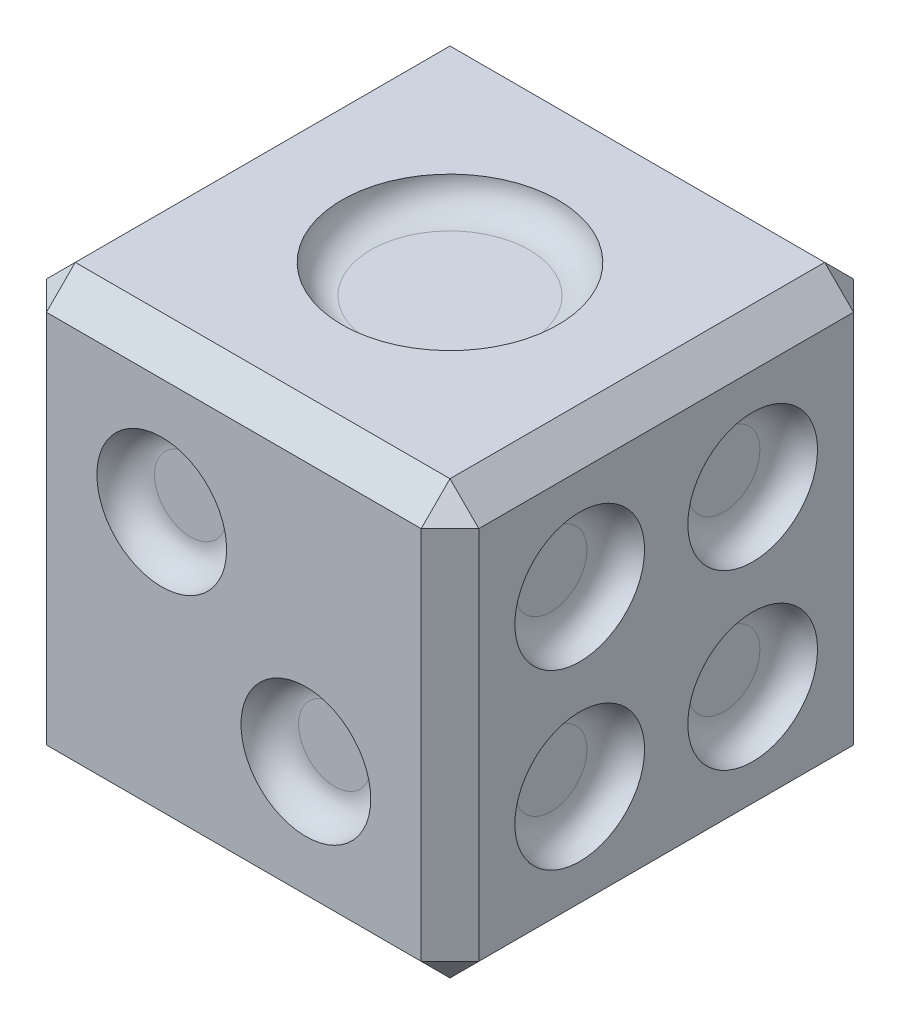
SolidWorks part; units mm, degrees
ref_plane "正面" through (0, 0, 0) normal (0, 0, 1) x (1, 0, 0)
ref_plane "平面" through (0, 0, 0) normal (0, 1, 0) x (1, 0, 0)
ref_plane "右側面" through (0, 0, 0) normal (1, 0, 0) x (0, 0, -1)
sketch "ｽｹｯﾁ3" plane through (0, 0, 0) normal (0, 1, 0) x (1, 0, 0)
  line L1 (0, 0) -> (30, 0)
  line L2 (0, 0) -> (0, 30)
  line L3 (0, 30) -> (30, 30)
  line L4 (30, 0) -> (30, 30)
  dimension "D1" = 30
  dimension "D2" = 30
extrude "ﾎﾞｽ - 押し出し2" add sketch "ｽｹｯﾁ3" along normal blind 30
chamfer "面取り1" distance 2 angle 45 12 edges at (0, 15, -30) (15, 30, -30) (0, 30, -15) (0, 15, 0) (15, 30, 0) (15, 0, 0) (0, 0, -15) (30, 15, 0) (30, 30, -15) (30, 15, -30) (15, 0, -30) (30, 0, -15)
sketch "ｽｹｯﾁ5" plane through (0, 30, 0) normal (0, 1, 0) x (1, 0, 0)
  line L0 (28, 0) -> (2, 0) construction
  line L1 (30, 28) -> (30, 2) construction
  circle A0 centre (15, 15) radius 7.5
  dimension "D3" = 15
  dimension "D1" = 15
  dimension "D2" = 15
extrude "ｶｯﾄ - 押し出し1" cut sketch "ｽｹｯﾁ5" against normal blind 2
fillet "ﾌｨﾚｯﾄ2" radius 2 1 edges at (15, 28, -7.5)
sketch "ｽｹｯﾁ8" plane through (0, 0, 0) normal (0, -1, 0) x (1, 0, 0)
  line L0 (0, -28) -> (0, -2) construction
  line L1 (2, 0) -> (28, 0) construction
  line L2 (28, -30) -> (2, -30) construction
  line L3 (30, -2) -> (30, -28) construction
  circle A0 centre (9, -7) radius 3.5
  circle A1 centre (9, -15) radius 3.5
  circle A2 centre (9, -23) radius 3.5
  circle A3 centre (21, -7) radius 3.5
  circle A4 centre (21, -15) radius 3.5
  circle A5 centre (21, -23) radius 3.5
  dimension "D13" = 7
  dimension "D14" = 7
  dimension "D15" = 7
  dimension "D16" = 7
  dimension "D17" = 7
  dimension "D18" = 7
  dimension "D1" = 9
  dimension "D2" = 7
  dimension "D3" = 15
  dimension "D4" = 7
  dimension "D5" = 9
  dimension "D6" = 9
  dimension "D7" = 7
  dimension "D8" = 9
  dimension "D9" = 15
  dimension "D10" = 9
  dimension "D11" = 9
  dimension "D12" = 7
extrude "ｶｯﾄ - 押し出し2" cut sketch "ｽｹｯﾁ8" against normal blind 2
fillet "ﾌｨﾚｯﾄ3" radius 2 6 edges at (21, 2, -26.5) (9, 2, -26.5) (9, 2, -18.5) (21, 2, -18.5) (21, 2, -10.5) (9, 2, -10.5)
sketch "ｽｹｯﾁ9" plane through (0, 0, 0) normal (0, 0, 1) x (1, 0, 0)
  line L0 (0, 2) -> (0, 28) construction
  line L1 (30, 28) -> (30, 2) construction
  line L2 (28, 0) -> (2, 0) construction
  line L3 (2, 30) -> (28, 30) construction
  circle A0 centre (10, 20) radius 4.5
  circle A1 centre (20, 10) radius 4.5
  dimension "D5" = 9
  dimension "D6" = 9
  dimension "D1" = 10
  dimension "D2" = 10
  dimension "D3" = 10
  dimension "D4" = 10
extrude "ｶｯﾄ - 押し出し3" cut sketch "ｽｹｯﾁ9" against normal blind 2
fillet "ﾌｨﾚｯﾄ4" radius 2 2 edges at (24.5, 10, -2) (14.5, 20, -2)
sketch "ｽｹｯﾁ10" plane through (0, 0, -30) normal (0, 0, -1) x (-1, 0, 0)
  line L0 (-28, 30) -> (-2, 30) construction
  line L1 (-30, 2) -> (-30, 28) construction
  line L2 (0, 28) -> (0, 2) construction
  line L3 (-2, 0) -> (-28, 0) construction
  circle A0 centre (-23, 23) radius 4
  circle A1 centre (-7, 23) radius 4
  circle A2 centre (-7, 7) radius 4
  circle A3 centre (-23, 7) radius 4
  circle A4 centre (-15, 15) radius 4
  dimension "D11" = 8
  dimension "D12" = 8
  dimension "D13" = 8
  dimension "D14" = 8
  dimension "D15" = 8
  dimension "D1" = 7
  dimension "D2" = 7
  dimension "D3" = 7
  dimension "D4" = 7
  dimension "D5" = 15
  dimension "D6" = 15
  dimension "D7" = 7
  dimension "D8" = 7
  dimension "D9" = 7
  dimension "D10" = 7
extrude "ｶｯﾄ - 押し出し4" cut sketch "ｽｹｯﾁ10" against normal blind 2
fillet "ﾌｨﾚｯﾄ5" radius 2 5 edges at (19, 7, -28) (3, 7, -28) (11, 15, -28) (3, 23, -28) (19, 23, -28)
sketch "ｽｹｯﾁ11" plane through (0, 0, 0) normal (-1, 0, 0) x (0, 0, 1)
  line L0 (-28, 30) -> (-2, 30) construction
  line L1 (-2, 0) -> (-28, 0) construction
  line L2 (-30, 2) -> (-30, 28) construction
  line L3 (0, 28) -> (0, 2) construction
  circle A0 centre (-23, 23) radius 4
  circle A1 centre (-15, 15) radius 4
  circle A2 centre (-7, 7) radius 4
  dimension "D7" = 8
  dimension "D8" = 8
  dimension "D9" = 8
  dimension "D1" = 7
  dimension "D2" = 15
  dimension "D3" = 7
  dimension "D4" = 7
  dimension "D5" = 15
  dimension "D6" = 7
extrude "ｶｯﾄ - 押し出し5" cut sketch "ｽｹｯﾁ11" against normal blind 2
fillet "ﾌｨﾚｯﾄ6" radius 2 3 edges at (2, 7, -3) (2, 15, -11) (2, 23, -19)
sketch "ｽｹｯﾁ12" plane through (30, 0, 0) normal (1, 0, 0) x (0, 0, -1)
  line L0 (2, 30) -> (28, 30) construction
  line L7 (28, 0) -> (2, 0) construction
  line L8 (0, 2) -> (0, 28) construction
  line L9 (30, 28) -> (30, 2) construction
  circle A0 centre (9, 21) radius 4.5
  circle A1 centre (21, 21) radius 4.5
  circle A2 centre (21, 9) radius 4.5
  circle A3 centre (9, 9) radius 4.5
  dimension "D9" = 9
  dimension "D10" = 9
  dimension "D11" = 9
  dimension "D12" = 9
  dimension "D1" = 9
  dimension "D2" = 9
  dimension "D3" = 9
  dimension "D4" = 9
  dimension "D5" = 9
  dimension "D6" = 9
  dimension "D7" = 9
  dimension "D8" = 9
extrude "ｶｯﾄ - 押し出し6" cut sketch "ｽｹｯﾁ12" against normal blind 2
fillet "ﾌｨﾚｯﾄ7" radius 2 4 edges at (28, 9, -13.5) (28, 9, -25.5) (28, 21, -25.5) (28, 21, -13.5)
